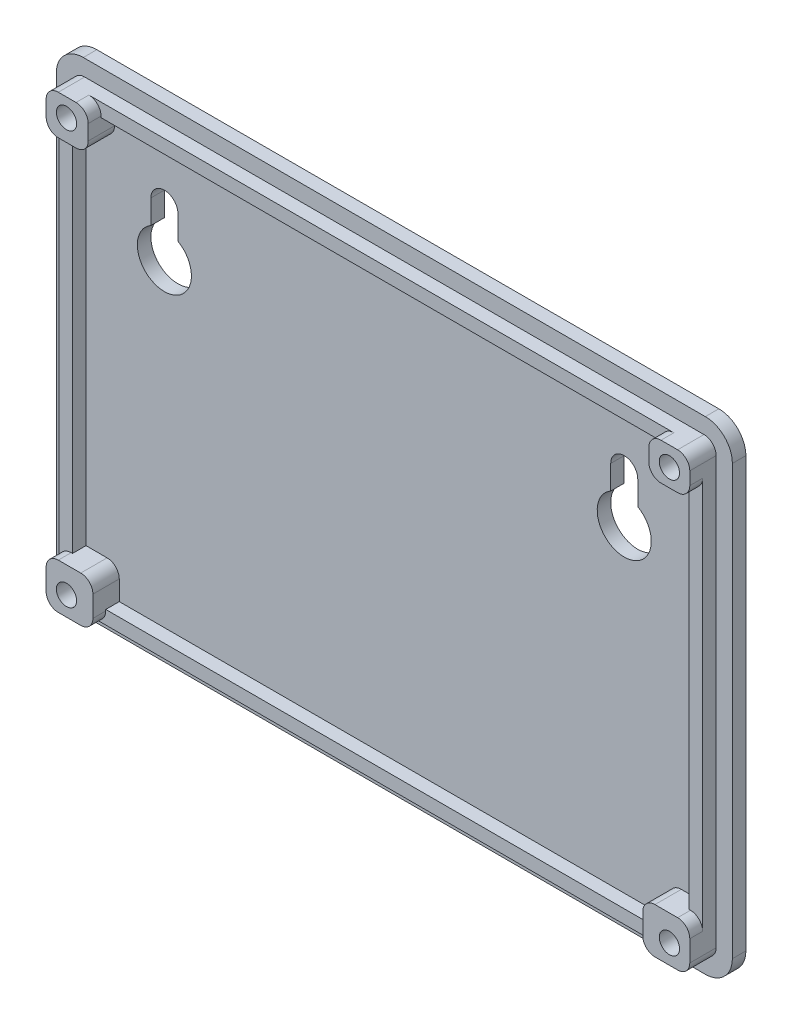
SolidWorks part; units mm, degrees
ref_plane "Спереди" through (0, 0, 0) normal (0, 0, 1) x (1, 0, 0)
ref_plane "Сверху" through (0, 0, 0) normal (0, 1, 0) x (1, 0, 0)
ref_plane "Справа" through (0, 0, 0) normal (1, 0, 0) x (0, 0, -1)
other "Configuration Table"
sketch "Эскиз1" plane through (0, 0, 0) normal (0, 0, 1) x (1, 0, 0)
  line L0 (36.025, 22.7375) -> (36.025, 19.2016)
  line L1 (32.025, 19.2016) -> (32.025, 22.7375)
  line L2 (-36.025, 19.2016) -> (-36.025, 22.7375)
  line L3 (-32.025, 22.7375) -> (-32.025, 19.2016)
  line L4 (41.5678, 31.3375) -> (-41.3989, 31.3375)
  line L5 (43.3678, 33.3375) -> (-43.1989, 33.3375)
  line L6 (47.625, -28.4259) -> (47.625, 29.6409)
  line L7 (45.625, -26.6259) -> (45.625, 27.8409)
  line L8 (45.825, 33.3375) -> (43.3678, 33.3375)
  line L9 (41.5678, 31.5375) -> (41.5678, 29.6409)
  line L10 (43.3678, 27.8409) -> (45.825, 27.8409)
  line L11 (47.625, 29.6409) -> (47.625, 31.5375)
  line L12 (-47.625, 31.5375) -> (-47.625, 29.2978)
  line L13 (-45.825, 27.4978) -> (-43.1989, 27.4978)
  line L14 (-41.3989, 29.2978) -> (-41.3989, 31.5375)
  line L15 (-43.1989, 33.3375) -> (-45.825, 33.3375)
  line L16 (-47.625, 29.2978) -> (-47.625, -28.4259)
  line L17 (-45.825, -26.6259) -> (-45.625, -26.6259)
  line L18 (-45.625, -26.6259) -> (-45.625, 27.4978)
  line L19 (-45.625, 27.4978) -> (-45.825, 27.4978)
  line L20 (-45.825, -33.3375) -> (-42.5024, -33.3375)
  line L21 (-40.7024, -31.5375) -> (-40.7024, -28.4259)
  line L22 (-42.5024, -26.6259) -> (-45.825, -26.6259)
  line L23 (-47.625, -28.4259) -> (-47.625, -31.5375)
  line L24 (40.6699, -31.3375) -> (-40.7024, -31.3375)
  line L25 (-40.7024, -31.3375) -> (-40.7024, -31.5375)
  line L26 (-42.5024, -33.3375) -> (42.4699, -33.3375)
  line L27 (40.6699, -31.5375) -> (40.6699, -31.3375)
  line L28 (40.6699, -28.4259) -> (40.6699, -31.5375)
  line L29 (42.4699, -33.3375) -> (45.825, -33.3375)
  line L30 (47.625, -31.5375) -> (47.625, -28.4259)
  line L31 (45.825, -26.6259) -> (42.4699, -26.6259)
  line L32 (46.025, 35.7375) -> (-46.025, 35.7375)
  line L33 (-50.025, 31.7375) -> (-50.025, -31.7375)
  line L34 (-46.025, -35.7375) -> (46.025, -35.7375)
  line L35 (50.025, -31.7375) -> (50.025, 31.7375)
  arc A0 (32.025, 19.2016) -> (36.025, 19.2016) centre (34.025, 15.7375) ccw
  arc A1 (36.025, 22.7375) -> (32.025, 22.7375) centre (34.025, 22.7375) ccw
  arc A2 (-36.025, 19.2016) -> (-32.025, 19.2016) centre (-34.025, 15.7375) ccw
  arc A3 (-32.025, 22.7375) -> (-36.025, 22.7375) centre (-34.025, 22.7375) ccw
  circle A4 centre (44.6087, 30.48) radius 1.5
  circle A5 centre (-44.6088, 30.6387) radius 1.5
  arc A6 (43.3678, 33.3375) -> (41.5678, 31.5375) centre (43.3678, 31.5375) ccw
  arc A7 (41.5678, 29.6409) -> (43.3678, 27.8409) centre (43.3678, 29.6409) ccw
  arc A8 (45.825, 27.8409) -> (47.625, 29.6409) centre (45.825, 29.6409) ccw
  arc A9 (47.625, 31.5375) -> (45.825, 33.3375) centre (45.825, 31.5375) ccw
  circle A10 centre (-44.6088, -30.48) radius 1.5
  arc A11 (-47.625, 29.2978) -> (-45.825, 27.4978) centre (-45.825, 29.2978) ccw
  arc A12 (-43.1989, 27.4978) -> (-41.3989, 29.2978) centre (-43.1989, 29.2978) ccw
  arc A13 (-41.3989, 31.5375) -> (-43.1989, 33.3375) centre (-43.1989, 31.5375) ccw
  arc A14 (-45.825, 33.3375) -> (-47.625, 31.5375) centre (-45.825, 31.5375) ccw
  arc A15 (-45.825, -26.6259) -> (-47.625, -28.4259) centre (-45.825, -28.4259) ccw
  arc A16 (-47.625, 29.2978) -> (-45.825, 27.4978) centre (-45.825, 29.2978) ccw
  circle A17 centre (44.6087, -30.48) radius 1.5
  arc A18 (-42.5024, -33.3375) -> (-40.7024, -31.5375) centre (-42.5024, -31.5375) ccw
  arc A19 (-40.7024, -28.4259) -> (-42.5024, -26.6259) centre (-42.5024, -28.4259) ccw
  arc A20 (-45.825, -26.6259) -> (-47.625, -28.4259) centre (-45.825, -28.4259) ccw
  arc A21 (-47.625, -31.5375) -> (-45.825, -33.3375) centre (-45.825, -31.5375) ccw
  arc A22 (-42.5024, -33.3375) -> (-40.7024, -31.5375) centre (-42.5024, -31.5375) ccw
  arc A23 (40.6699, -31.5375) -> (42.4699, -33.3375) centre (42.4699, -31.5375) ccw
  arc A24 (40.6699, -31.5375) -> (42.4699, -33.3375) centre (42.4699, -31.5375) ccw
  arc A25 (45.825, -33.3375) -> (47.625, -31.5375) centre (45.825, -31.5375) ccw
  arc A26 (47.625, -28.4259) -> (45.825, -26.6259) centre (45.825, -28.4259) ccw
  arc A27 (42.4699, -26.6259) -> (40.6699, -28.4259) centre (42.4699, -28.4259) ccw
  arc A28 (50.025, 31.7375) -> (46.025, 35.7375) centre (46.025, 31.7375) ccw
  arc A29 (-46.025, 35.7375) -> (-50.025, 31.7375) centre (-46.025, 31.7375) ccw
  arc A30 (-50.025, -31.7375) -> (-46.025, -35.7375) centre (-46.025, -31.7375) ccw
  arc A31 (46.025, -35.7375) -> (50.025, -31.7375) centre (46.025, -31.7375) ccw
sketch "Эскиз2" plane through (0, 0, 0) normal (0, 0, 1) x (1, 0, 0)
  line L0 (36.025, 22.7375) -> (36.025, 19.2016) construction
  line L1 (32.025, 19.2016) -> (32.025, 22.7375) construction
  line L2 (-36.025, 19.2016) -> (-36.025, 22.7375) construction
  line L3 (-32.025, 22.7375) -> (-32.025, 19.2016) construction
  line L4 (-50.025, 31.7375) -> (-50.025, -31.7375) construction
  line L5 (-46.025, -35.7375) -> (46.025, -35.7375) construction
  line L6 (50.025, -31.7375) -> (50.025, 31.7375) construction
  line L7 (46.025, 35.7375) -> (-46.025, 35.7375) construction
  line L8 (36.025, 22.7375) -> (36.025, 19.2016)
  line L9 (32.025, 19.2016) -> (32.025, 22.7375)
  line L10 (-36.025, 19.2016) -> (-36.025, 22.7375)
  line L11 (-32.025, 22.7375) -> (-32.025, 19.2016)
  line L12 (-50.025, 31.7375) -> (-50.025, -31.7375)
  line L13 (-46.025, -35.7375) -> (46.025, -35.7375)
  line L14 (50.025, -31.7375) -> (50.025, 31.7375)
  line L15 (46.025, 35.7375) -> (-46.025, 35.7375)
  arc A0 (36.025, 22.7375) -> (32.025, 22.7375) centre (34.025, 22.7375) ccw construction
  arc A1 (32.025, 19.2016) -> (36.025, 19.2016) centre (34.025, 15.7375) ccw construction
  arc A2 (-32.025, 22.7375) -> (-36.025, 22.7375) centre (-34.025, 22.7375) ccw construction
  arc A3 (-36.025, 19.2016) -> (-32.025, 19.2016) centre (-34.025, 15.7375) ccw construction
  circle A4 centre (-44.6088, -30.48) radius 1.5 construction
  circle A5 centre (44.6087, -30.48) radius 1.5 construction
  circle A6 centre (44.6087, 30.48) radius 1.5 construction
  circle A7 centre (-44.6088, 30.6387) radius 1.5 construction
  arc A8 (-46.025, 35.7375) -> (-50.025, 31.7375) centre (-46.025, 31.7375) ccw construction
  arc A9 (-50.025, -31.7375) -> (-46.025, -35.7375) centre (-46.025, -31.7375) ccw construction
  arc A10 (46.025, -35.7375) -> (50.025, -31.7375) centre (46.025, -31.7375) ccw construction
  arc A11 (50.025, 31.7375) -> (46.025, 35.7375) centre (46.025, 31.7375) ccw construction
  arc A12 (36.025, 22.7375) -> (32.025, 22.7375) centre (34.025, 22.7375) ccw
  arc A13 (32.025, 19.2016) -> (36.025, 19.2016) centre (34.025, 15.7375) ccw
  arc A14 (-32.025, 22.7375) -> (-36.025, 22.7375) centre (-34.025, 22.7375) ccw
  arc A15 (-36.025, 19.2016) -> (-32.025, 19.2016) centre (-34.025, 15.7375) ccw
  circle A16 centre (-44.6088, -30.48) radius 1.5
  circle A17 centre (44.6087, -30.48) radius 1.5
  circle A18 centre (44.6087, 30.48) radius 1.5
  circle A19 centre (-44.6088, 30.6387) radius 1.5
  arc A20 (-46.025, 35.7375) -> (-50.025, 31.7375) centre (-46.025, 31.7375) ccw
  arc A21 (-50.025, -31.7375) -> (-46.025, -35.7375) centre (-46.025, -31.7375) ccw
  arc A22 (46.025, -35.7375) -> (50.025, -31.7375) centre (46.025, -31.7375) ccw
  arc A23 (50.025, 31.7375) -> (46.025, 35.7375) centre (46.025, 31.7375) ccw
extrude "Бобышка-Вытянуть1" add sketch "Эскиз2" along normal blind 2
sketch "Эскиз4" plane through (0, 0, 2) normal (0, 0, 1) x (1, 0, 0)
  line L0 (-47.625, 29.2978) -> (-47.625, -28.4259) construction
  line L1 (-45.625, -26.6259) -> (-45.625, 27.4978) construction
  line L2 (43.3678, 33.3375) -> (-43.1989, 33.3375) construction
  line L3 (41.5678, 31.3375) -> (-41.3989, 31.3375) construction
  line L4 (-47.625, 29.2978) -> (-47.625, -28.4259)
  line L5 (-45.625, -26.6259) -> (-45.625, 27.4978)
  line L6 (43.3678, 33.3375) -> (-43.1989, 33.3375)
  line L7 (41.5678, 31.3375) -> (-41.3989, 31.3375)
  line L8 (-43.1989, 33.3375) -> (-45.825, 33.3375) construction
  line L9 (-47.625, 31.5375) -> (-47.625, 29.2978) construction
  line L10 (-45.825, 27.4978) -> (-43.1989, 27.4978) construction
  line L11 (-41.3989, 29.2978) -> (-41.3989, 31.5375) construction
  line L12 (-43.1989, 33.3375) -> (-45.825, 33.3375)
  line L13 (-47.625, 31.5375) -> (-47.625, 29.2978)
  line L14 (-45.825, 27.4978) -> (-43.1989, 27.4978)
  line L15 (-41.3989, 29.2978) -> (-41.3989, 31.5375)
  line L16 (47.625, -28.4259) -> (47.625, 29.6409) construction
  line L17 (45.625, -26.6259) -> (45.625, 27.8409) construction
  line L18 (47.625, -28.4259) -> (47.625, 29.6409)
  line L19 (45.625, -26.6259) -> (45.625, 27.8409)
  line L20 (47.625, 29.6409) -> (47.625, 31.5375) construction
  line L21 (45.825, 33.3375) -> (43.3678, 33.3375) construction
  line L22 (43.3678, 27.8409) -> (45.825, 27.8409) construction
  line L23 (41.5678, 31.5375) -> (41.5678, 29.6409) construction
  line L24 (47.625, 29.6409) -> (47.625, 31.5375)
  line L25 (45.825, 33.3375) -> (43.3678, 33.3375)
  line L26 (43.3678, 27.8409) -> (45.825, 27.8409)
  line L27 (41.5678, 31.5375) -> (41.5678, 29.6409)
  line L28 (-42.5024, -33.3375) -> (42.4699, -33.3375) construction
  line L29 (40.6699, -31.3375) -> (-40.7024, -31.3375) construction
  line L30 (-42.5024, -33.3375) -> (42.4699, -33.3375)
  line L31 (40.6699, -31.3375) -> (-40.7024, -31.3375)
  line L32 (-45.825, -33.3375) -> (-42.5024, -33.3375) construction
  line L33 (-47.625, -28.4259) -> (-47.625, -31.5375) construction
  line L34 (-40.7024, -31.5375) -> (-40.7024, -28.4259) construction
  line L35 (-42.5024, -26.6259) -> (-45.825, -26.6259) construction
  line L36 (-45.825, -33.3375) -> (-42.5024, -33.3375)
  line L37 (-47.625, -28.4259) -> (-47.625, -31.5375)
  line L38 (-40.7024, -31.5375) -> (-40.7024, -28.4259)
  line L39 (-42.5024, -26.6259) -> (-45.825, -26.6259)
  line L40 (47.625, -31.5375) -> (47.625, -28.4259) construction
  line L41 (42.4699, -33.3375) -> (45.825, -33.3375) construction
  line L42 (40.6699, -28.4259) -> (40.6699, -31.5375) construction
  line L43 (45.825, -26.6259) -> (42.4699, -26.6259) construction
  line L44 (47.625, -31.5375) -> (47.625, -28.4259)
  line L45 (42.4699, -33.3375) -> (45.825, -33.3375)
  line L46 (40.6699, -28.4259) -> (40.6699, -31.5375)
  line L47 (45.825, -26.6259) -> (42.4699, -26.6259)
  arc A0 (-45.825, 33.3375) -> (-47.625, 31.5375) centre (-45.825, 31.5375) ccw construction
  arc A1 (-43.1989, 27.4978) -> (-41.3989, 29.2978) centre (-43.1989, 29.2978) ccw construction
  arc A2 (-45.825, 33.3375) -> (-47.625, 31.5375) centre (-45.825, 31.5375) ccw
  arc A3 (-43.1989, 27.4978) -> (-41.3989, 29.2978) centre (-43.1989, 29.2978) ccw
  circle A4 centre (-44.6088, 30.6387) radius 1.5 construction
  circle A5 centre (-44.6088, 30.6387) radius 1.5
  circle A6 centre (44.6087, 30.48) radius 1.5 construction
  circle A7 centre (44.6087, 30.48) radius 1.5
  arc A8 (47.625, 31.5375) -> (45.825, 33.3375) centre (45.825, 31.5375) ccw construction
  arc A9 (41.5678, 29.6409) -> (43.3678, 27.8409) centre (43.3678, 29.6409) ccw construction
  arc A10 (47.625, 31.5375) -> (45.825, 33.3375) centre (45.825, 31.5375) ccw
  arc A11 (41.5678, 29.6409) -> (43.3678, 27.8409) centre (43.3678, 29.6409) ccw
  circle A12 centre (-44.6088, -30.48) radius 1.5 construction
  circle A13 centre (-44.6088, -30.48) radius 1.5
  arc A14 (-47.625, -31.5375) -> (-45.825, -33.3375) centre (-45.825, -31.5375) ccw construction
  arc A15 (-40.7024, -28.4259) -> (-42.5024, -26.6259) centre (-42.5024, -28.4259) ccw construction
  arc A16 (-47.625, -31.5375) -> (-45.825, -33.3375) centre (-45.825, -31.5375) ccw
  arc A17 (-40.7024, -28.4259) -> (-42.5024, -26.6259) centre (-42.5024, -28.4259) ccw
  arc A18 (45.825, -33.3375) -> (47.625, -31.5375) centre (45.825, -31.5375) ccw construction
  circle A19 centre (44.6087, -30.48) radius 1.5 construction
  arc A20 (42.4699, -26.6259) -> (40.6699, -28.4259) centre (42.4699, -28.4259) ccw construction
  arc A21 (45.825, -33.3375) -> (47.625, -31.5375) centre (45.825, -31.5375) ccw
  circle A22 centre (44.6087, -30.48) radius 1.5
  arc A23 (42.4699, -26.6259) -> (40.6699, -28.4259) centre (42.4699, -28.4259) ccw
  circle M21 centre (44.6087, 30.48) radius 1.5
  circle M22 centre (-44.6088, -30.48) radius 1.5
  circle M35 centre (44.6087, -30.48) radius 1.5
  circle M36 centre (-44.6088, 30.6387) radius 1.5
extrude "Бобышка-Вытянуть2" add sketch "Эскиз4" along normal blind 2 contours L45 A21 L44 L18 L24 A10 L25 L6 L12 A2 L13 L4 L37 A16 L36 L30 L47 A23 L46 L31 L38 A17 L39 L5 L14 A3 L15 L7 L27 A11 M22 M35 M36 M21 region at (-46.4623, 30.4177, 2)
sketch "Эскиз5" plane through (0, 0, 4) normal (0, 0, 1) x (1, 0, 0)
  line L0 (-43.1989, 33.3375) -> (-45.825, 33.3375) construction
  line L1 (-47.625, 31.5375) -> (-47.625, 29.2978) construction
  line L2 (-45.825, 27.4978) -> (-43.1989, 27.4978) construction
  line L3 (-41.3989, 29.2978) -> (-41.3989, 31.5375) construction
  line L4 (-43.1989, 33.3375) -> (-45.825, 33.3375)
  line L5 (-47.625, 31.5375) -> (-47.625, 29.2978)
  line L6 (-45.825, 27.4978) -> (-43.1989, 27.4978)
  line L7 (-41.3989, 29.2978) -> (-41.3989, 31.5375)
  line L8 (41.5678, 31.5375) -> (41.5678, 29.6409) construction
  line L9 (43.3678, 27.8409) -> (45.825, 27.8409) construction
  line L10 (47.625, 29.6409) -> (47.625, 31.5375) construction
  line L11 (45.825, 33.3375) -> (43.3678, 33.3375) construction
  line L12 (41.5678, 31.5375) -> (41.5678, 29.6409)
  line L13 (43.3678, 27.8409) -> (45.825, 27.8409)
  line L14 (47.625, 29.6409) -> (47.625, 31.5375)
  line L15 (45.825, 33.3375) -> (43.3678, 33.3375)
  line L16 (-47.625, -28.4259) -> (-47.625, -31.5375) construction
  line L17 (-45.825, -33.3375) -> (-42.5024, -33.3375) construction
  line L18 (-40.7024, -31.5375) -> (-40.7024, -28.4259) construction
  line L19 (-42.5024, -26.6259) -> (-45.825, -26.6259) construction
  line L20 (-47.625, -28.4259) -> (-47.625, -31.5375)
  line L21 (-45.825, -33.3375) -> (-42.5024, -33.3375)
  line L22 (-40.7024, -31.5375) -> (-40.7024, -28.4259)
  line L23 (-42.5024, -26.6259) -> (-45.825, -26.6259)
  line L24 (40.6699, -28.4259) -> (40.6699, -31.5375) construction
  line L25 (42.4699, -33.3375) -> (45.825, -33.3375) construction
  line L26 (47.625, -31.5375) -> (47.625, -28.4259) construction
  line L27 (45.825, -26.6259) -> (42.4699, -26.6259) construction
  line L28 (40.6699, -28.4259) -> (40.6699, -31.5375)
  line L29 (42.4699, -33.3375) -> (45.825, -33.3375)
  line L30 (47.625, -31.5375) -> (47.625, -28.4259)
  line L31 (45.825, -26.6259) -> (42.4699, -26.6259)
  arc A0 (-45.825, 33.3375) -> (-47.625, 31.5375) centre (-45.825, 31.5375) ccw construction
  arc A1 (-47.625, 29.2978) -> (-45.825, 27.4978) centre (-45.825, 29.2978) ccw construction
  arc A2 (-43.1989, 27.4978) -> (-41.3989, 29.2978) centre (-43.1989, 29.2978) ccw construction
  arc A3 (-41.3989, 31.5375) -> (-43.1989, 33.3375) centre (-43.1989, 31.5375) ccw construction
  circle A4 centre (-44.6088, 30.6387) radius 1.5 construction
  arc A5 (-45.825, 33.3375) -> (-47.625, 31.5375) centre (-45.825, 31.5375) ccw
  arc A6 (-47.625, 29.2978) -> (-45.825, 27.4978) centre (-45.825, 29.2978) ccw
  arc A7 (-43.1989, 27.4978) -> (-41.3989, 29.2978) centre (-43.1989, 29.2978) ccw
  arc A8 (-41.3989, 31.5375) -> (-43.1989, 33.3375) centre (-43.1989, 31.5375) ccw
  circle A9 centre (-44.6088, 30.6387) radius 1.5
  arc A10 (43.3678, 33.3375) -> (41.5678, 31.5375) centre (43.3678, 31.5375) ccw construction
  arc A11 (41.5678, 29.6409) -> (43.3678, 27.8409) centre (43.3678, 29.6409) ccw construction
  arc A12 (45.825, 27.8409) -> (47.625, 29.6409) centre (45.825, 29.6409) ccw construction
  arc A13 (47.625, 31.5375) -> (45.825, 33.3375) centre (45.825, 31.5375) ccw construction
  circle A14 centre (44.6087, 30.48) radius 1.5 construction
  arc A15 (43.3678, 33.3375) -> (41.5678, 31.5375) centre (43.3678, 31.5375) ccw
  arc A16 (41.5678, 29.6409) -> (43.3678, 27.8409) centre (43.3678, 29.6409) ccw
  arc A17 (45.825, 27.8409) -> (47.625, 29.6409) centre (45.825, 29.6409) ccw
  arc A18 (47.625, 31.5375) -> (45.825, 33.3375) centre (45.825, 31.5375) ccw
  circle A19 centre (44.6087, 30.48) radius 1.5
  arc A20 (-47.625, -31.5375) -> (-45.825, -33.3375) centre (-45.825, -31.5375) ccw construction
  arc A21 (-42.5024, -33.3375) -> (-40.7024, -31.5375) centre (-42.5024, -31.5375) ccw construction
  arc A22 (-40.7024, -28.4259) -> (-42.5024, -26.6259) centre (-42.5024, -28.4259) ccw construction
  arc A23 (-45.825, -26.6259) -> (-47.625, -28.4259) centre (-45.825, -28.4259) ccw construction
  circle A24 centre (-44.6088, -30.48) radius 1.5 construction
  arc A25 (-47.625, -31.5375) -> (-45.825, -33.3375) centre (-45.825, -31.5375) ccw
  arc A26 (-42.5024, -33.3375) -> (-40.7024, -31.5375) centre (-42.5024, -31.5375) ccw
  arc A27 (-40.7024, -28.4259) -> (-42.5024, -26.6259) centre (-42.5024, -28.4259) ccw
  arc A28 (-45.825, -26.6259) -> (-47.625, -28.4259) centre (-45.825, -28.4259) ccw
  circle A29 centre (-44.6088, -30.48) radius 1.5
  arc A30 (42.4699, -26.6259) -> (40.6699, -28.4259) centre (42.4699, -28.4259) ccw construction
  arc A31 (40.6699, -31.5375) -> (42.4699, -33.3375) centre (42.4699, -31.5375) ccw construction
  arc A32 (45.825, -33.3375) -> (47.625, -31.5375) centre (45.825, -31.5375) ccw construction
  arc A33 (47.625, -28.4259) -> (45.825, -26.6259) centre (45.825, -28.4259) ccw construction
  circle A34 centre (44.6087, -30.48) radius 1.5 construction
  arc A35 (42.4699, -26.6259) -> (40.6699, -28.4259) centre (42.4699, -28.4259) ccw
  arc A36 (40.6699, -31.5375) -> (42.4699, -33.3375) centre (42.4699, -31.5375) ccw
  arc A37 (45.825, -33.3375) -> (47.625, -31.5375) centre (45.825, -31.5375) ccw
  arc A38 (47.625, -28.4259) -> (45.825, -26.6259) centre (45.825, -28.4259) ccw
  circle A39 centre (44.6087, -30.48) radius 1.5
extrude "Бобышка-Вытянуть3" add sketch "Эскиз5" along normal blind 1.9
chamfer "Фаска1" distance 1 angle 45 4 edges at (46.1087, 30.48, 0) (46.1087, -30.48, 0) (-43.1088, -30.48, 0) (-43.1088, 30.6387, 0)
